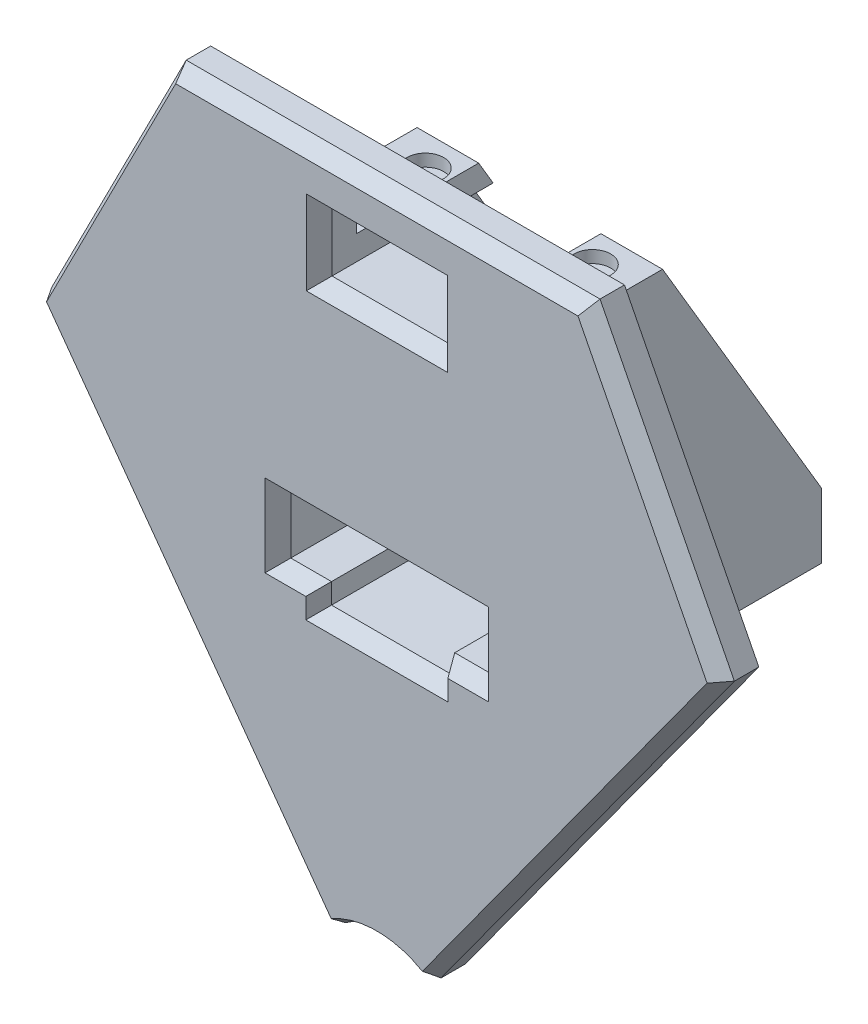
SolidWorks part; units mm, degrees
ref_plane "Front Plane" through (0, 0, 0) normal (0, 0, 1) x (1, 0, 0)
ref_plane "Top Plane" through (0, 0, 0) normal (0, 1, 0) x (1, 0, 0)
ref_plane "Right Plane" through (0, 0, 0) normal (1, 0, 0) x (0, 0, -1)
sketch "Sketch2" plane through (0, 0, 0) normal (0, 1, 0) x (1, 0, 0)
  line L0 (15.061, 0) -> (15.061, 32)
  line L1 (-12.561, 2.5) -> (12.561, 2.5)
  line L2 (-12.561, 2.5) -> (-12.561, 32)
  line L4 (12.561, 2.5) -> (12.561, 32)
  line L5 (15.061, 32) -> (12.561, 32)
  line L7 (-15.061, 32) -> (-15.061, 0)
  line L8 (-15.061, 0) -> (15.061, 0)
  line L10 (-15.061, 32) -> (-12.561, 32)
  point P4 (0, 2.5)
  point P12 (0, 0)
  dimension "D1" = 2.5
  dimension "D2" = 2.5
  dimension "D3" = 29.5
  dimension "D4" = 25.122
extrude "Boss-Extrude1" add sketch "Sketch2" along normal blind 32.5
sketch "Sketch4" plane through (0, 0, 0) normal (0, -1, 0) x (1, 0, 0)
  line L10 (-7.561, -6) -> (-7.561, 0)
  line L13 (-12.561, -2.5) -> (-12.561, -32) construction
  line L18 (-12.561, -10) -> (-7.561, -6)
  line L23 (12.561, -32) -> (12.561, -2.5) construction
  line L26 (12.561, -10) -> (7.561, -6)
  line L33 (-15.061, -32) -> (-15.061, 0) construction
  line L36 (15.061, 0) -> (15.061, -32) construction
  line L38 (-7.561, 0) -> (-15.061, 0)
  line L39 (7.561, -6) -> (7.561, 0)
  line L40 (7.561, 0) -> (15.061, 0)
  line L41 (-15.061, 0) -> (-15.061, -32)
  line L42 (-15.061, -32) -> (-12.561, -32)
  line L43 (-12.561, -32) -> (-15.061, -32) construction
  line L44 (-12.561, -32) -> (-12.561, -10)
  line L45 (12.561, -10) -> (12.561, -32)
  line L46 (12.561, -32) -> (15.061, -32)
  line L47 (15.061, -32) -> (15.061, 0)
  circle A2 centre (-10.2499, -4.95) radius 1.05
  circle A5 centre (10.2499, -4.95) radius 1.05
  dimension "D4" = 6
  dimension "D5" = 2.1
  dimension "D1" = 7.5
  dimension "D2" = 7.5
  dimension "D3" = 10
extrude "Boss-Extrude2" add sketch "Sketch4" along normal blind 2.5
sketch "Sketch5" plane through (0, 32.5, 0) normal (0, 1, 0) x (1, 0, 0)
  line L0 (-15.061, 32) -> (-10.2499, 32)
  line L9 (-10.2499, 32) -> (-6.25, 26)
  line L13 (-15.061, 0) -> (15.061, 0) construction
  line L14 (15.061, 0) -> (-15.061, 0)
  line L15 (-15.061, 0) -> (-15.061, 32)
  line L20 (15.061, 0) -> (15.061, 32)
  line L21 (-6.25, 26) -> (6.25, 26)
  line L22 (6.25, 26) -> (10.2499, 32)
  line L23 (10.2499, 32) -> (15.061, 32)
  circle A0 centre (-10.2499, 4.95) radius 1.05 construction
  circle A1 centre (-10.2499, 8.7) radius 1.05
  circle A2 centre (10.2499, 8.7) radius 1.05
  point P6 (0, 26)
  dimension "D4" = 0
  dimension "D1" = 8.7
  dimension "D2" = 12.5
  dimension "D3" = 20.4998
  dimension "D5" = 6
extrude "Boss-Extrude3" add sketch "Sketch5" along normal blind 3
sketch "Sketch6" plane through (-15.061, 0, 0) normal (-1, 0, 0) x (0, 0, 1)
  line L0 (-12.5, 35.5) -> (-32, 2.5)
  line L1 (-32, 2.5) -> (-32, 35.5)
  line L2 (-32, 35.5) -> (-12.5, 35.5)
  line L3 (-32, 35.5) -> (-32, -2.5) construction
  line L4 (-32, 35.5) -> (0, 35.5) construction
  line L6 (0, -2.5) -> (-32, -2.5) construction
  line L7 (0, 35.5) -> (0, -2.5) construction
  dimension "D1" = 5
  dimension "D2" = 12.5
extrude "Cut-Extrude1" cut sketch "Sketch6" against normal through all
ref_plane "Plane1" through (0, 16.5, 0) normal (0, -1, 0) x (-1, 0, 0)
sketch "Sketch13" plane through (0, 0, 0) normal (0, 0, 1) x (1, 0, 0)
  line L1 (-15.061, 35.5) -> (15.061, 35.5)
  line L2 (-15.061, 35.5) -> (-15.061, -2.5)
  line L3 (-15.061, -2.5) -> (15.061, -2.5)
  line L4 (15.061, 35.5) -> (15.061, -2.5)
extrude "Boss-Extrude7" add sketch "Sketch13" along normal blind 2.5
sketch "Sketch8" plane through (0, 0, 2.5) normal (0, 0, 1) x (1, 0, 0)
  line L0 (0, -43.5) -> (-43.5926, 16.5)
  line L1 (-16.5671, 16.5) -> (16.5671, 16.5) construction
  line L2 (-43.5926, 16.5) -> (43.5926, 16.5)
  line L3 (43.5926, 16.5) -> (0, -43.5)
  dimension "D1" = 72
  dimension "D2" = 60
extrude "Boss-Extrude4" add sketch "Sketch8" along normal blind 5
sketch "Sketch9" plane through (0, 0, 2.5) normal (0, 0, 1) x (1, 0, 0)
  line L0 (43.5926, 16.5) -> (65.3888, 46.5)
  line L1 (65.3888, 46.5) -> (-65.3888, 46.5)
  line L2 (-65.3888, 46.5) -> (-43.5926, 16.5)
  line L3 (43.5926, 16.5) -> (-43.5926, 16.5)
  line L4 (0, -43.5) -> (43.5926, 16.5) construction
  line L5 (-43.5926, 16.5) -> (0, -43.5) construction
  dimension "D1" = 30
extrude "Boss-Extrude6" add sketch "Sketch9" along normal up to surface (5 mm away) up to face at (0, -3.5, 7.5)
sketch "Sketch10" plane through (0, 0, 2.5) normal (0, 0, -1) x (-1, 0, 0)
  line L25 (-25.3888, 46.5) -> (-65.3888, 46.5)
  line L26 (-65.3888, 46.5) -> (65.3888, 46.5) construction
  line L27 (-65.3888, 46.5) -> (-41.8774, 14.1393)
  line L28 (0, -43.5) -> (-65.3888, 46.5) construction
  line L29 (-41.8774, 14.1393) -> (-25.3888, 46.5)
  line L30 (65.3888, 46.5) -> (41.8774, 14.1393)
  line L31 (65.3888, 46.5) -> (0, -43.5) construction
  line L32 (41.8774, 14.1393) -> (25.3888, 46.5)
  line L33 (25.3888, 46.5) -> (65.3888, 46.5)
  dimension "D1" = 40
extrude "Cut-Extrude2" cut sketch "Sketch10" against normal through all
sketch "Sketch14" plane through (0, 0, -2.5) normal (0, 0, -1) x (-1, 0, 0)
  line L11 (-7.561, -2.5) -> (7.561, -2.5)
  line L12 (15.061, -2.5) -> (-15.061, -2.5) construction
  line L13 (7.561, -2.5) -> (7.561, 0)
  line L14 (12.561, 0) -> (7.561, 0) construction
  line L15 (7.561, -2.5) -> (7.561, 0) construction
  line L16 (7.561, 0) -> (12.561, 0)
  line L17 (12.561, 0) -> (12.561, 7.7837)
  line L18 (12.561, 2.5) -> (12.561, 32.5) construction
  line L19 (12.561, 7.7837) -> (-12.561, 7.7837)
  line L20 (-12.561, 32.5) -> (-12.561, 2.5) construction
  line L21 (-12.561, 7.7837) -> (-12.561, 0)
  line L22 (-12.561, 2.5) -> (-12.561, -2.5) construction
  line L23 (-7.561, 0) -> (-12.561, 0) construction
  line L24 (-12.561, 0) -> (-7.561, 0)
  line L25 (-7.561, 0) -> (-7.561, -2.5)
  line L26 (-7.561, -2.5) -> (-12.561, -2.5) construction
  line L27 (-15.061, 35.5) -> (15.061, 35.5) construction
  line L28 (-7.5, 35.5) -> (7.5, 35.5)
  line L29 (-7.5, 35.5) -> (-7.5, 40.5)
  line L30 (-7.5, 40.5) -> (7.5, 40.5)
  line L31 (7.5, 35.5) -> (7.5, 40.5)
  point P37 (0, 35.5)
  dimension "D1" = 15
  dimension "D2" = 5
extrude "Cut-Extrude3" cut sketch "Sketch14" against normal through all
sketch "Sketch15" plane through (0, -2.5, 0) normal (0, -1, 0) x (1, 0, 0)
  line L1 (15.061, -32) -> (-15.061, -32)
  line L2 (15.061, -32) -> (15.061, 2.5)
  line L3 (15.061, 2.5) -> (-15.061, 2.5)
  line L4 (-15.061, -32) -> (-15.061, 2.5)
  circle A0 centre (-10.2499, -4.95) radius 2.495
  circle A1 centre (10.341, -4.95) radius 2.495
  dimension "D1" = 4.99
  dimension "D2" = 4.99
extrude "Boss-Extrude8" add sketch "Sketch15" along normal blind 3
sketch "Sketch17" plane through (0, -5.5, 0) normal (0, -1, 0) x (1, 0, 0)
  line L0 (15.061, 2.5) -> (-15.061, 2.5) construction
  circle A0 centre (0, -37.5) radius 13.75
  dimension "D2" = 27.5
  dimension "D1" = 40
extrude "Cut-Extrude4" cut sketch "Sketch17" against normal through all
sketch "Sketch19" plane through (0, 0, -2.5) normal (0, 0, -1) x (-1, 0, 0)
  line L0 (-15.061, 35.5) -> (15.061, 35.5) construction
  line L1 (7.5, 35.5) -> (-7.5, 35.5)
  line L2 (7.5, 35.5) -> (7.5, 32.5)
  line L3 (7.5, 32.5) -> (-7.5, 32.5)
  line L4 (-7.5, 35.5) -> (-7.5, 32.5)
  line L5 (7.5, 35.5) -> (7.5, 40.5) construction
  line L6 (-7.5, 40.5) -> (-7.5, 35.5) construction
  line L7 (-12.561, 32.5) -> (12.561, 32.5) construction
  dimension "D1" = 0
  dimension "D2" = 0
  dimension "D3" = 0
extrude "Cut-Extrude6" cut sketch "Sketch19" along normal through all both and the other way through all
sketch "Sketch21" plane through (0, 35.5, 0) normal (0, 1, 0) x (1, 0, 0)
  circle A0 centre (-10.2499, 8.7) radius 2.25
  circle A1 centre (10.2499, 8.7) radius 2.25
  dimension "D1" = 4.5
  dimension "D2" = 4.5
extrude "Cut-Extrude8" cut sketch "Sketch21" against normal blind 1.5
ref_axis "Axis1" through (0, -43.5, 11.5724) along (0, 0, -1)
sketch "Sketch20" plane through (0, 0, 2.5) normal (0, 0, -1) x (-1, 0, 0)
  circle A0 centre (0, -43.5) radius 10
  dimension "D1" = 20
extrude "Cut-Extrude7" cut sketch "Sketch20" against normal through all
chamfer "Chamfer1" distance 2 angle 30 18 edges at (-23.8776, -10.6353, 7.5) (-33.6331, 30.3197, 7.5) (0, 46.5, 7.5) (33.6331, 30.3197, 7.5) (23.8776, -10.6353, 7.5) (7.5, 36.5, 7.5) (0, 40.5, 7.5) (-7.5, 36.5, 7.5) (0, 32.5, 7.5) (12.561, 3.8918, 7.5) (0, 7.7837, 7.5) (-12.561, 3.8918, 7.5) (-10.061, 0, 7.5) (-7.561, -1.25, 7.5) (0, -2.5, 7.5) (7.561, -1.25, 7.5) (10.061, 0, 7.5) (0, -33.5, 7.5) first distance on face at (-23.8776, -10.6353, 5) first distance on face at (-33.6331, 30.3197, 5) first distance on face at (0, 46.5, 5) first distance on face at (33.6331, 30.3197, 5) first distance on face at (23.8776, -10.6353, 5) first distance on face at (7.5, 35.6429, -1.3247) first distance on face at (0, 40.5, 5) first distance on face at (-7.5, 35.6429, -1.3247) first distance on face at (0, 32.5, 2.5) first distance on face at (12.561, 8.6917, -9.7874) first distance on face at (0, 7.7837, 2.5) first distance on face at (-12.561, 8.6917, -9.7874) first distance on face at (-10.061, 0, -0.25) first distance on face at (-7.561, -1.25, 0.75) first distance on face at (0, -2.5, -9.0821) first distance on face at (7.561, -1.25, 0.75) first distance on face at (10.061, 0, -0.25) first distance on face at (0, -34.4549, 5)
